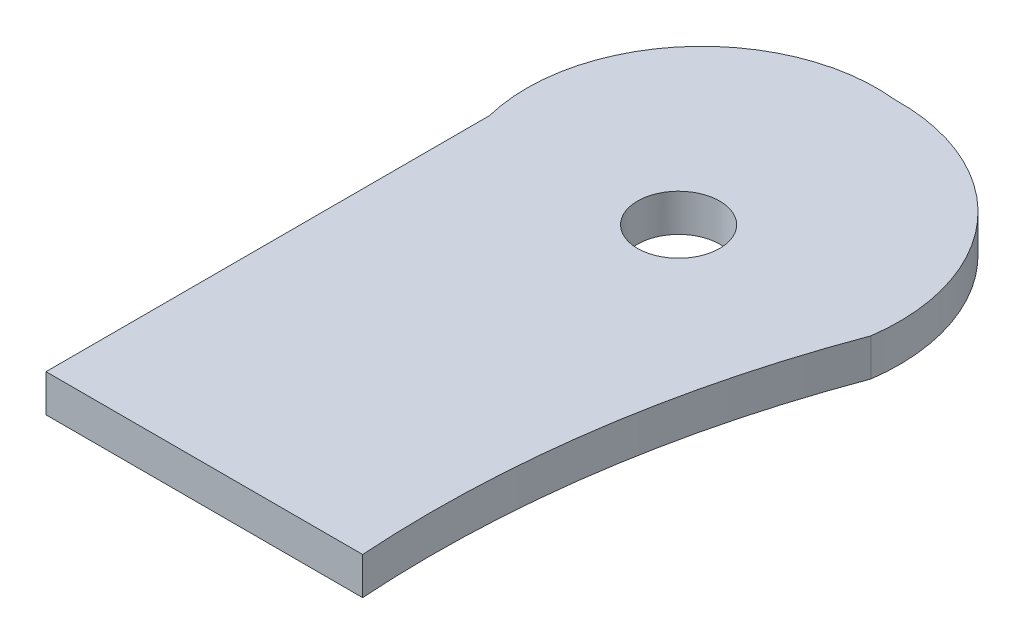
SolidWorks part; units mm, degrees
ref_plane "Front Plane" through (0, 0, 0) normal (0, 0, 1) x (1, 0, 0)
ref_plane "Top Plane" through (0, 0, 0) normal (0, 1, 0) x (1, 0, 0)
ref_plane "Right Plane" through (0, 0, 0) normal (1, 0, 0) x (0, 0, -1)
sketch "Sketch1" plane through (0, 0, 0) normal (0, 1, 0) x (1, 0, 0)
  line L0 (-7.9375, 0) -> (-56.1578, 0) construction
  line L1 (7.9375, 0) -> (57.15, 0) construction
  line L2 (0, 7.9375) -> (0, 64.2938) construction
  line L3 (-56.1578, 0) -> (-56.1578, -131.7625)
  line L4 (-56.1578, -131.7625) -> (37.9016, -131.7625)
  line L5 (-7.9375, 0) -> (0, 7.9375) construction
  line L6 (0, 7.9375) -> (7.9375, 0) construction
  line L7 (-3.9688, 3.9688) -> (-5.6127, 5.6127) construction
  line L8 (3.9688, 3.9688) -> (5.6127, 5.6127) construction
  line L9 (-5.6127, 5.6127) -> (-45.7432, 45.7432) construction
  line L10 (5.6127, 5.6127) -> (44.34, 44.34) construction
  circle A0 centre (0, 0) radius 7.9375
  arc A1 (37.9016, -131.7625) -> (57.15, 0) centre (352.2811, -110.4012) cw
  arc A2 (-56.1578, 0) -> (0, 64.2938) centre (-5.6524, 12.5583) cw
  arc A3 (0, 64.2938) -> (57.15, 0) centre (1.2712, 7.8769) cw
  dimension "D1" = 15.875
  dimension "D2" = 48.2203
  dimension "D3" = 49.2125
  dimension "D4" = 56.3562
  dimension "D5" = 131.7625
  dimension "D6" = 94.0594
  dimension "D7" = 56.7531
  dimension "D8" = 54.7687
extrude "Boss-Extrude1" add sketch "Sketch1" along normal blind 11.1125
sketch "Sketch2" plane through (0, 11.1125, 0) normal (0, 1, 0) x (1, 0, 0)
  circle A0 centre (0, 0) radius 12.2039
  dimension "D1" = 24.4078
extrude "Cut-Extrude1" cut sketch "Sketch2" against normal up to surface (11.1125 mm away) up to face at (-5.2401, 0, 34.0668)
